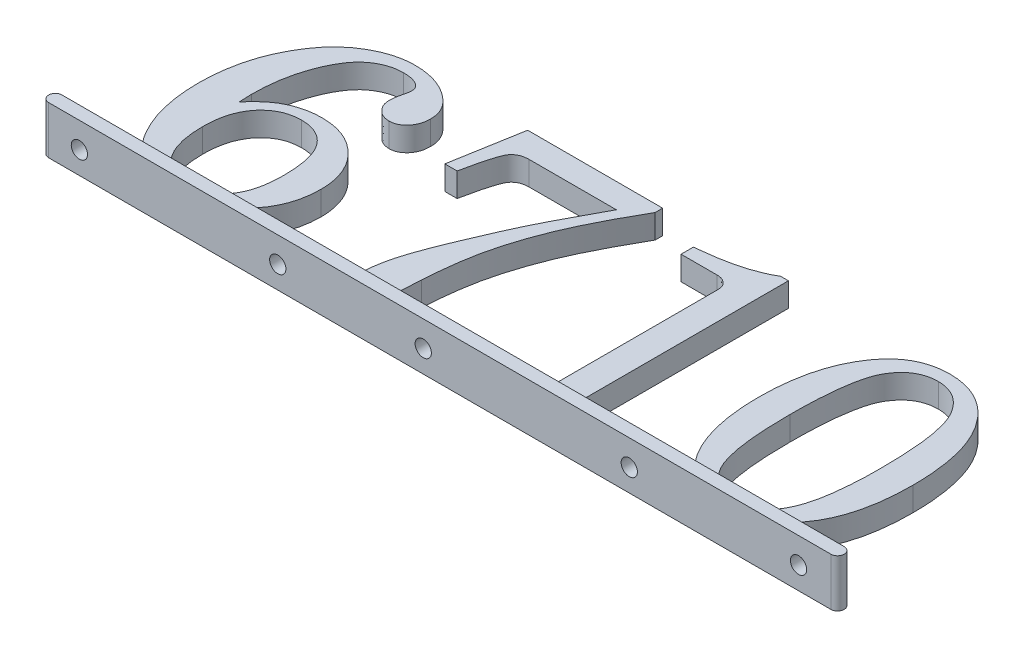
SolidWorks part; units mm, degrees
ref_plane "Front Plane" through (0, 0, 0) normal (0, 0, 1) x (1, 0, 0)
ref_plane "Top Plane" through (0, 0, 0) normal (0, 1, 0) x (1, 0, 0)
ref_plane "Right Plane" through (0, 0, 0) normal (1, 0, 0) x (0, 0, -1)
sketch "Sketch3" plane through (0, 0, 0) normal (0, 1, 0) x (1, 0, 0)
  text T0 "6710" font "Century Schoolbook" height 50
extrude "Boss-Extrude1" add sketch "Sketch3" along normal blind 5
sketch "Sketch4" plane through (2.6119, 0, 2.5188) normal (0, 1, 0) x (1, 0, 0)
  line L0 (-92.7694, -22.5827) -> (70.6796, -22.5827) construction
  line L1 (-92.7694, -21.1977) -> (70.6796, -21.1977)
  line L2 (-92.7694, -23.9677) -> (70.6796, -23.9677)
  arc A0 (-92.7694, -21.1977) -> (-92.7694, -23.9677) centre (-92.7694, -22.5827) ccw
  arc A1 (70.6796, -23.9677) -> (70.6796, -21.1977) centre (70.6796, -22.5827) ccw
  point P2 (-11.0449, -22.5827)
extrude "Boss-Extrude2" add sketch "Sketch4" along normal blind 10 contours L1 A1 L2 A0
hole_wizard "M3 Clearance Hole2" positions "Sketch8" profile "Sketch7" hole size "M3" standard "ANSI Metric" end condition through all
sketch "Sketch8" plane through (0, 0, 23.7165) normal (0, 0, -1) x (-1, 0, 0)
  point P0 (83.7533, 4.6606)
  point P2 (42.2985, 4.6606)
  point P4 (11.8998, 4.6606)
  point P6 (-31.151, 4.6606)
  point P8 (-66.5202, 4.6606)
sketch "Sketch7" plane through (-83.7533, 4.6606, 23.7165) normal (1, 0, 0) x (0, 1, 0)
  line L0 (0, 0) -> (0, 2.77)
  line L1 (0, 2.77) -> (1.7, 2.77)
  line L2 (1.7, 2.77) -> (1.7, 0)
  line L5 (1.7, 0) -> (0, 0)
  line L11 (0, -6.35) -> (0, 107.95) construction
  dimension "Thru Hole Dia." = 3.4
  dimension "Thru Hole Depth" = 2.77
